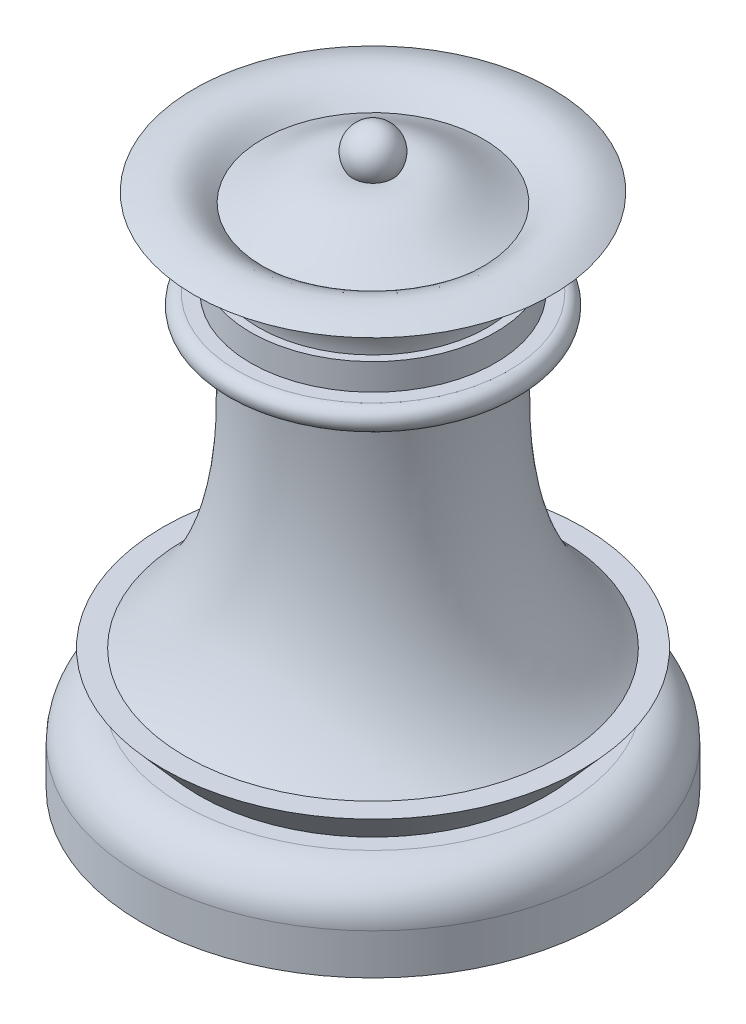
SolidWorks part; units mm, degrees
ref_plane "Front Plane" through (0, 0, 0) normal (0, 0, 1) x (1, 0, 0)
ref_plane "Top Plane" through (0, 0, 0) normal (0, 1, 0) x (1, 0, 0)
ref_plane "Right Plane" through (0, 0, 0) normal (1, 0, 0) x (0, 0, -1)
sketch "Эскиз1" plane through (0, 0, 0) normal (0, 0, 1) x (1, 0, 0)
  line L0 (-28.3192, 10) -> (-21.3192, 10)
  line L1 (0, 0) -> (-28.3192, 0)
  line L4 (-28.3192, 0) -> (-28.3192, 10)
  line L7 (-23, 15) -> (-25.7019, 15)
  line L9 (-14, 50) -> (-18, 50)
  line L10 (-18, 50) -> (-18, 52.746)
  line L11 (-18, 52.746) -> (-15, 52.746)
  line L12 (-15, 52.746) -> (-15, 55.996)
  line L13 (-15, 55.996) -> (-14, 55.996)
  line L14 (-25.7019, 15) -> (-21.3192, 10)
  line L15 (0, 70.6319) -> (0, 0) construction
  line L16 (0, 0) -> (0, 70.6319)
  arc A1 (0, 70.6319) -> (-2.4564, 66.0511) centre (0, 67.6829) ccw
  spline S0 degree 2 poles (-14, 50) (-11.5494, 24.7439) (-23, 15) knots 0 0 0 0.889446 0.889446 0.889446
  spline S1 degree 3 poles (-14, 55.996) (-14.1619, 59.6537) (-17.0706, 63.9321) (-21.9055, 63.4047) knots 0 0 0 0 1 1 1 1
  spline S2 degree 3 poles (-21.9055, 63.4047) (-17.4934, 65.5345) (-15.6739, 64.2216) (-13.5116, 62.2675) knots 0 0 0 0 1 1 1 1
  spline S3 degree 3 poles (-13.5116, 62.2675) (-8.6648, 64.2988) (-7.2126, 66.9205) (-2.4564, 66.0511) knots 0 0 0 0 0.620902 0.620902 0.620902 0.620902
  point P2 (0, 0)
  point P6 (0, 0)
  dimension "D1" = 18
  dimension "D2" = 2.746
  dimension "D3" = 15
  dimension "D4" = 3.25
  dimension "D5" = 14.6359
  dimension "D6" = 35
  dimension "D7" = 5
  dimension "D8" = 10
revolve "Повернуть11" add sketch "Эскиз1" angle 360 about L15
fillet "Скругление1" 2 edges at (0, 52.746, 18) (0, 50, 18) type full round first side face at (0, 52.746, 18) second side face at (0, 50, 14) middle face at (0, 50, 18)
fillet "Скругление7" radius 5 1 edges at (0, 10, 28.3192) type face fillet first side face at (0, 10, 28.3192) second side face at (0, 0, 28.3192)
